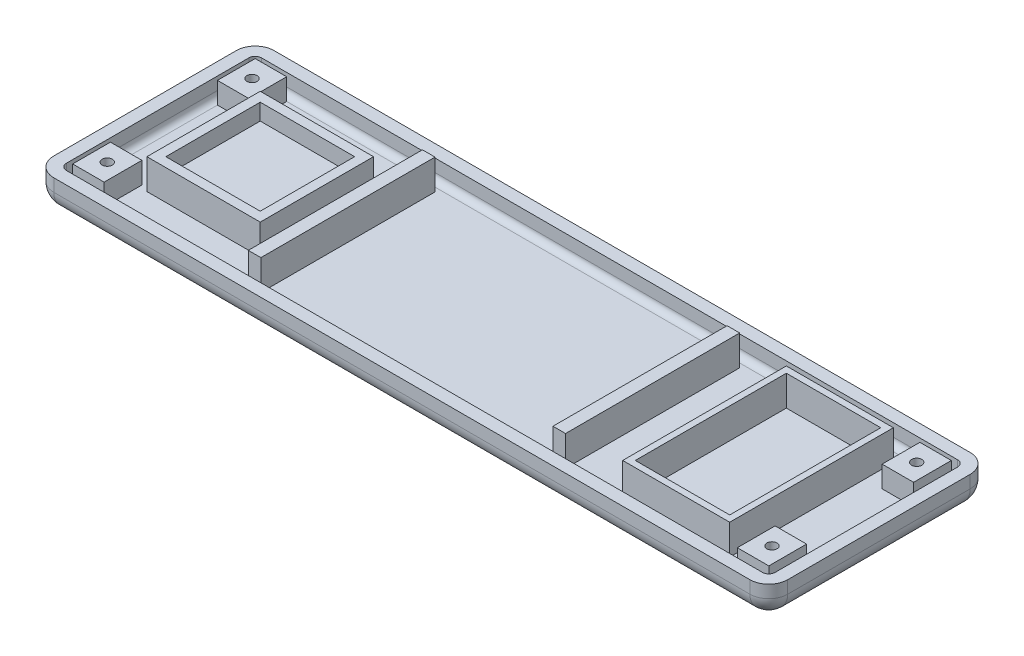
SolidWorks part; units mm, degrees
note: '?' marks a value the reader was unsure of.
ref_plane "Front Plane" through (0, 0, 0) normal (0, 0, 1) x (1, 0, 0)
ref_plane "Top Plane" through (0, 0, 0) normal (0, 1, 0) x (1, 0, 0)
ref_plane "Right Plane" through (0, 0, 0) normal (1, 0, 0) x (0, 0, -1)
sketch "Sketch1" plane through (0, 0, 0) normal (0, 1, 0) x (1, 0, 0)
  line L1 (-74.041, 22.225) -> (74.041, 22.225)
  line L2 (-74.041, 22.225) -> (-74.041, -22.225)
  line L3 (-74.041, -22.225) -> (74.041, -22.225)
  line L4 (74.041, 22.225) -> (74.041, -22.225)
extrude "Boss-Extrude1" add sketch "Sketch1" along normal blind 6.35
fillet "Fillet1" radius 3.81 8 edges at (0, 0, -22.225) (-74.041, 0, 0) (74.041, 0, 0) (0, 0, 22.225) (74.041, 3.175, 22.225) (74.041, 3.175, -22.225) (-74.041, 3.175, -22.225) (-74.041, 3.175, 22.225)
shell "Shell1" thickness 2.54 removed face at (0, 6.35, 0)
sketch "Sketch3" plane through (0, 2.54, 0) normal (0, 1, 0) x (1, 0, 0)
  line L1 (-70.231, 18.415) -> (-63.881, 18.415)
  line L2 (-70.231, 18.415) -> (-70.231, 10.795)
  line L3 (-70.231, 10.795) -> (-63.881, 10.795)
  line L4 (-63.881, 18.415) -> (-63.881, 10.795)
  line L5 (70.231, 18.415) -> (63.881, 18.415)
  line L6 (70.231, 18.415) -> (70.231, 10.795)
  line L7 (70.231, 10.795) -> (63.881, 10.795)
  line L8 (63.881, 18.415) -> (63.881, 10.795)
  line L9 (-70.231, -18.415) -> (-63.881, -18.415)
  line L10 (-70.231, -18.415) -> (-70.231, -10.795)
  line L11 (-70.231, -10.795) -> (-63.881, -10.795)
  line L12 (-63.881, -18.415) -> (-63.881, -10.795)
  line L14 (70.231, -18.415) -> (63.881, -18.415)
  line L15 (70.231, -18.415) -> (70.231, -10.795)
  line L16 (70.231, -10.795) -> (63.881, -10.795)
  line L17 (63.881, -18.415) -> (63.881, -10.795)
  line L21 (-70.231, -18.415) -> (-70.231, 18.415) construction
  line L22 (70.231, -18.415) -> (-70.231, -18.415) construction
  dimension "D1" = 7.62
  dimension "D2" = 6.35
  dimension "D3" = 7.62
  dimension "D4" = 6.35
  dimension "D5" = 7.62
  dimension "D6" = 6.35
  dimension "D7" = 7.62
  dimension "D8" = 6.35
extrude "Boss-Extrude2" add sketch "Sketch3" along normal blind 4.318
ref_plane "Plane1" through (0, 2.54, 0) normal (0, 1, 0) x (1, 0, 0)
sketch "Sketch5" plane through (0, 2.54, 0) normal (0, 1, 0) x (1, 0, 0)
  line L1 (-62.23, -11.43) -> (-39.37, -11.43)
  line L2 (-62.23, -11.43) -> (-62.23, 11.43)
  line L3 (-62.23, 11.43) -> (-39.37, 11.43)
  line L4 (-39.37, -11.43) -> (-39.37, 11.43)
extrude "Boss-Extrude3" add sketch "Sketch5" along normal blind 6.096
ref_point "Point1"
sketch "Sketch7" plane through (0, 8.636, 0) normal (0, 1, 0) x (1, 0, 0)
  line L1 (-41.275, -9.525) -> (-60.325, -9.525)
  line L2 (-41.275, -9.525) -> (-41.275, 9.525)
  line L3 (-41.275, 9.525) -> (-60.325, 9.525)
  line L4 (-60.325, -9.525) -> (-60.325, 9.525)
  line L5 (-41.275, -9.525) -> (-60.325, 9.525) construction
  line L6 (-41.275, 9.525) -> (-60.325, -9.525) construction
  point P0 (-50.8, 0)
  dimension "D1" = 19.05
  dimension "D2" = 19.05
extrude "Cut-Extrude1" cut sketch "Sketch7" against normal blind 3.302
sketch "Sketch8" plane through (0, 2.54, 0) normal (0, 1, 0) x (1, 0, 0)
  line L1 (60.4345, -16.51) -> (38.8445, -16.51)
  line L2 (60.4345, -16.51) -> (60.4345, 16.51)
  line L3 (60.4345, 16.51) -> (38.8445, 16.51)
  line L4 (38.8445, -16.51) -> (38.8445, 16.51)
  line L5 (60.4345, -16.51) -> (38.8445, 16.51) construction
  line L6 (60.4345, 16.51) -> (38.8445, -16.51) construction
  point P0 (49.6395, 0)
  dimension "D1" = 21.59
  dimension "D2" = 33.02
extrude "Boss-Extrude4" add sketch "Sketch8" along normal blind 6.096
sketch "Sketch9" plane through (0, 2.54, 0) normal (0, 1, 0) x (1, 0, 0)
  line L1 (-35.6377, -17.5679) -> (-33.0977, -17.5679)
  line L2 (-35.6377, -17.5679) -> (-35.6377, 17.5679)
  line L3 (-35.6377, 17.5679) -> (-33.0977, 17.5679)
  line L4 (-33.0977, -17.5679) -> (-33.0977, 17.5679)
  line L5 (-35.6377, -17.5679) -> (-33.0977, 17.5679) construction
  line L6 (-35.6377, 17.5679) -> (-33.0977, -17.5679) construction
  line L7 (25.8303, -17.5679) -> (28.3703, -17.5679)
  line L8 (25.8303, -17.5679) -> (25.8303, 17.5679)
  line L9 (25.8303, 17.5679) -> (28.3703, 17.5679)
  line L10 (28.3703, -17.5679) -> (28.3703, 17.5679)
  line L11 (25.8303, -17.5679) -> (28.3703, 17.5679) construction
  line L12 (25.8303, 17.5679) -> (28.3703, -17.5679) construction
  point P0 (-34.3677, 0)
  point P5 (27.1003, 0)
  dimension "D1" = 2.54
  dimension "D2" = 2.54
  dimension "D3" = 58.928
extrude "Boss-Extrude5" add sketch "Sketch9" along normal blind 6.096
ref_point "Point2"
ref_point "Point3"
ref_point "Point4"
ref_point "Point5"
ref_point "Point6"
sketch "Sketch12" plane through (0, 8.636, 0) normal (0, 1, 0) x (1, 0, 0)
  line L1 (59.1645, 15.24) -> (40.1145, 15.24)
  line L2 (59.1645, 15.24) -> (59.1645, -15.24)
  line L3 (59.1645, -15.24) -> (40.1145, -15.24)
  line L4 (40.1145, 15.24) -> (40.1145, -15.24)
  line L5 (59.1645, 15.24) -> (40.1145, -15.24) construction
  line L6 (59.1645, -15.24) -> (40.1145, 15.24) construction
  point P0 (49.6395, 0)
  dimension "D1" = 30.48
  dimension "D2" = 19.05
extrude "Cut-Extrude2" cut sketch "Sketch12" against normal up to surface (6.096 mm away) up to face at (-34.3677, 2.54, 0)
hole_wizard "CBORE for #1 Pan Head Machine Screw2" [suppressed] positions "Sketch14" profile "Sketch13" counterbore size "#1" standard "ANSI Inch"
sketch "Sketch14" plane through (0, 0, 0) normal (0, -1, 0) x (-1, 0, 0)
  point P0 (-66.6734, 14.5009)
  point P2 (-66.6734, -14.6377)
  point P4 (66.4014, -14.6377)
  point P6 (66.4014, 14.5009)
sketch "Sketch13" plane through (66.6734, 0, -14.5009) normal (1, 0, 0) x (0, 0, -1)
  line L0 (0, 0) -> (0, 8.636)
  line L1 (0, 8.636) -> (1.0287, 8.636)
  line L2 (3.9141, 2.54) -> (-3.7059, 2.54) construction
  line L3 (1.0287, 8.636) -> (1.0287, 1.3462)
  line L4 (1.0287, 1.3462) -> (2.1831, 1.3462)
  line L5 (2.1831, 1.3462) -> (2.1831, 0)
  line L7 (2.1831, 0) -> (0, 0)
  line L11 (0, -6.35) -> (0, 107.95) construction
  dimension "Thru Hole Dia." = 2.0574
  dimension "Thru Hole Depth" = 8.636
  dimension "C'Bore Dia." = 4.3663
  dimension "C'Bore Depth" = 1.3462
ref_axis "Axis2" through (67.056, 6.858, -14.605) along (0, -1, 0)?
hole_wizard "CBORE for #1 Pan Head Machine Screw3" positions "Sketch24" profile "Sketch23" counterbore size "#1" standard "ANSI Inch" end condition through all
sketch "Sketch24" plane through (0, 0, 0) normal (0, -1, 0) x (-1, 0, 0)
  point P0 (-67.056, 14.605)
  point P3 (-67.056, -14.605)
  point P6 (67.056, -14.605)
  point P9 (67.056, 14.605)
sketch "Sketch23" plane through (67.056, 0, -14.605) normal (1, 0, 0) x (0, 0, -1)
  line L0 (0, 0) -> (0, 8.636)
  line L1 (0, 8.636) -> (1.0287, 8.636)
  line L3 (1.0287, 8.636) -> (1.0287, 1.3462)
  line L4 (1.0287, 1.3462) -> (2.1831, 1.3462)
  line L5 (2.1831, 1.3462) -> (2.1831, 0)
  line L7 (2.1831, 0) -> (0, 0)
  line L11 (0, -6.35) -> (0, 107.95) construction
  dimension "Thru Hole Dia." = 2.0574
  dimension "Thru Hole Depth" = 8.636
  dimension "C'Bore Dia." = 4.3663
  dimension "C'Bore Depth" = 1.3462
